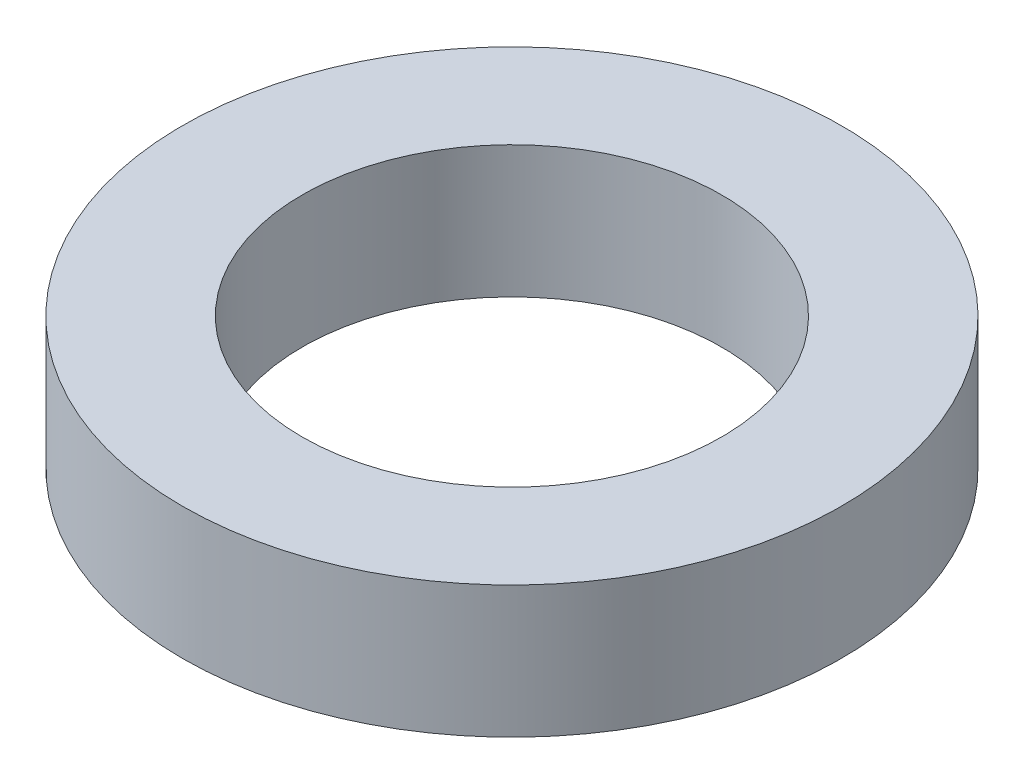
SolidWorks part; units mm, degrees
ref_plane "Front Plane" through (0, 0, 0) normal (0, 0, 1) x (1, 0, 0)
ref_plane "Top Plane" through (0, 0, 0) normal (0, 1, 0) x (1, 0, 0)
ref_plane "Right Plane" through (0, 0, 0) normal (1, 0, 0) x (0, 0, -1)
sketch "Sketch1" plane through (0, 0, 0) normal (0, 1, 0) x (1, 0, 0)
  circle A0 centre (0, 0) radius 55
  dimension "FLANGE_OD" = 110
extrude "Boss-Extrude1" add sketch "Sketch1" along normal blind 22
sketch "Sketch2" plane through (0, 0, 0) normal (0, 1, 0) x (1, 0, 0)
  circle A0 centre (0, 0) radius 35
  dimension "BORE_D" = 70
extrude "Cut-Extrude1" cut sketch "Sketch2" along normal through all
sketch "Sketch3" plane through (0, 22, 0) normal (0, 1, 0) x (1, 0, 0)
  circle A0 centre (0, 0) radius 21.91 construction
  circle A1 centre (-21.91, 0) radius 1.8866
  dimension "BOLT_D" = 3.7731
  dimension "BOLT_PCD" = 43.8201
extrude "Cut-Extrude2" cut sketch "Sketch3" against normal blind 17.1059 rebuild error yes
pattern_circular "CirPattern1" count 4 over 360 rebuild error yes
